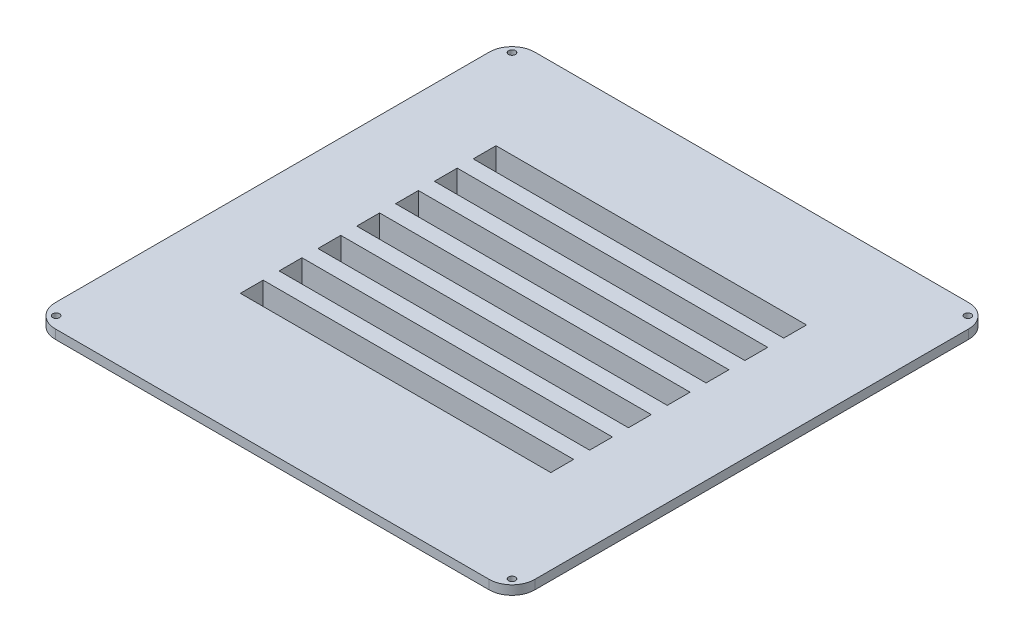
SolidWorks part; units mm, degrees
ref_plane "Front Plane" through (0, 0, 0) normal (0, 0, 1) x (1, 0, 0)
ref_plane "Top Plane" through (0, 0, 0) normal (0, 1, 0) x (1, 0, 0)
ref_plane "Right Plane" through (0, 0, 0) normal (1, 0, 0) x (0, 0, -1)
sketch "Sketch1" plane through (0, 0, 0) normal (0, 1, 0) x (1, 0, 0)
  line L0 (-101, -101) -> (-101, 101)
  line L5 (-105, -105) -> (105, -105)
  line L6 (-105, -105) -> (-105, 105)
  line L7 (-105, 105) -> (105, 105)
  line L8 (105, -105) -> (105, 105)
  line L9 (-101, 101) -> (101, 101)
  line L10 (101, -101) -> (101, 101)
  line L11 (-101, -101) -> (101, -101)
  line L12 (-101, 101) -> (-99.8333, 99.8333) construction
  line L13 (-55, 0) -> (55, 0) construction
  line L14 (-101, -101) -> (-99.8333, -99.8333) construction
  line L15 (0, -55) -> (0, 55) construction
  line L16 (101, -101) -> (99.8333, -99.8333) construction
  line L17 (101, 101) -> (99.8333, 99.8333) construction
  circle A1 centre (-99.8333, 99.8333) radius 1.5
  circle A2 centre (-99.8333, -99.8333) radius 1.5
  circle A3 centre (99.8333, -99.8333) radius 1.5
  circle A4 centre (99.8333, 99.8333) radius 1.5
  point P0 (0, 0)
  point P6 (-105, 0)
  point P7 (0, 105)
  dimension "D3" = 4
  dimension "D4" = 3
  dimension "D1" = 210
  dimension "D2" = 210
  dimension "D5" = 1.65
  dimension "D6" = 45
extrude "MainExtrude" add sketch "Sketch1" along normal blind 4 contours L6 L5 L8 L7
extrude "ScrewHoles" cut sketch "Sketch1<6>" along normal up to surface (4 mm away) contours A1 | A2 | A3 | A4 up to face at (0, 4, 0)
sketch "Sketch1<6>" plane through (0, 0, 0) normal (0, 1, 0) x (1, 0, 0) same geometry as "Sketch1"
fillet "RoundedCorners" radius 10 4 edges at (-105, 2, -105) (-105, 2, 105) (105, 2, -105) (105, 2, 105)
sketch "Sketch3" plane through (0, 0, 0) normal (0, 1, 0) x (1, 0, 0)
  line L2 (-68, 61) -> (-68, 51)
  line L4 (68, 61) -> (68, 51)
  line L17 (-68, 56) -> (68, 56) construction
  line L19 (-68, 39) -> (68, 39) construction
  line L21 (-68, 22) -> (68, 22) construction
  line L23 (-68, 5) -> (68, 5) construction
  line L24 (-68, 51) -> (68, 51)
  line L30 (-68, -12) -> (68, -12) construction
  line L32 (-68, -29) -> (68, -29) construction
  line L34 (-68, -46) -> (68, -46) construction
  line L58 (-68, 34) -> (68, 34)
  line L59 (-68, 17) -> (68, 17)
  line L60 (-68, 0) -> (68, 0)
  line L61 (-68, -17) -> (68, -17)
  line L62 (-68, -34) -> (68, -34)
  line L65 (-68, -51) -> (68, -51)
  line L66 (-68, 61) -> (68, 61)
  line L97 (-68, 44) -> (68, 44)
  line L98 (-68, 27) -> (68, 27)
  line L106 (-68, 10) -> (68, 10)
  line L107 (-68, -7) -> (68, -7)
  line L135 (-68, -24) -> (68, -24)
  line L136 (-68, -41) -> (68, -41)
  line L140 (68, 44) -> (68, 34)
  line L141 (-68, 44) -> (-68, 34)
  line L142 (-68, 27) -> (-68, 17)
  line L143 (68, 27) -> (68, 17)
  line L144 (-68, 10) -> (-68, 0)
  line L145 (68, 10) -> (68, 0)
  line L146 (-68, -7) -> (-68, -17)
  line L147 (68, -7) -> (68, -17)
  line L148 (-68, -24) -> (-68, -34)
  line L149 (68, -24) -> (68, -34)
  line L150 (-68, -41) -> (-68, -51)
  line L151 (68, -41) -> (68, -51)
  point P47 (0, 0)
  dimension "D1" = 5
  dimension "D2" = 5
  dimension "D3" = 17
  dimension "D4" = 17
  dimension "D5" = 17
  dimension "D6" = 17
  dimension "D7" = 17
  dimension "D8" = 17
  dimension "D9" = 136
sketch "Sketch4" plane through (0, 0, 0) normal (0, 1, 0) x (1, 0, 0)
  line L1 (-68, -51) -> (68, -51) construction
  line L2 (-68, -46) -> (68, -46) construction
  line L3 (-68, -41) -> (68, -41) construction
  line L4 (-68, -34) -> (68, -34) construction
  line L5 (-68, -29) -> (68, -29) construction
  line L6 (-68, -24) -> (68, -24) construction
  line L7 (-68, -17) -> (68, -17) construction
  line L8 (-68, -12) -> (68, -12) construction
  line L9 (-68, -7) -> (68, -7) construction
  line L10 (-68, 0) -> (68, 0) construction
  line L11 (-68, 5) -> (68, 5) construction
  line L12 (-68, 10) -> (68, 10) construction
  line L13 (-68, 17) -> (68, 17) construction
  line L14 (-68, 22) -> (68, 22) construction
  line L15 (-68, 27) -> (68, 27) construction
  line L16 (-68, 34) -> (68, 34) construction
  line L17 (-68, 39) -> (68, 39) construction
  line L18 (-68, 44) -> (68, 44) construction
  line L19 (68, 61) -> (68, 51) construction
  line L20 (-68, 51) -> (68, 51) construction
  line L21 (-68, 56) -> (68, 56) construction
  line L22 (-68, 61) -> (68, 61) construction
  line L23 (-68, 61) -> (-68, 51) construction
  line L26 (-68, -51) -> (68, -51)
  line L27 (-68, -46) -> (68, -46) construction
  line L28 (-68, -41) -> (68, -41)
  line L29 (-68, -34) -> (68, -34)
  line L30 (-68, -29) -> (68, -29) construction
  line L31 (-68, -24) -> (68, -24)
  line L32 (-68, -17) -> (68, -17)
  line L33 (-68, -12) -> (68, -12) construction
  line L34 (-68, -7) -> (68, -7)
  line L35 (-68, 0) -> (68, 0)
  line L36 (-68, 5) -> (68, 5) construction
  line L37 (-68, 10) -> (68, 10)
  line L38 (-68, 17) -> (68, 17)
  line L39 (-68, 22) -> (68, 22) construction
  line L40 (-68, 27) -> (68, 27)
  line L41 (-68, 34) -> (68, 34)
  line L42 (-68, 39) -> (68, 39) construction
  line L43 (-68, 44) -> (68, 44)
  line L44 (68, 61) -> (68, 51)
  line L45 (-68, 51) -> (68, 51)
  line L46 (-68, 56) -> (68, 56) construction
  line L47 (-68, 61) -> (68, 61)
  line L48 (-68, 61) -> (-68, 51)
  line L50 (68, 44) -> (68, 34)
  line L51 (-68, 44) -> (-68, 34)
  line L52 (-68, 27) -> (-68, 17)
  line L53 (68, 27) -> (68, 17)
  line L54 (-68, 10) -> (-68, 0)
  line L55 (68, 10) -> (68, 0)
  line L56 (-68, -7) -> (-68, -17)
  line L57 (68, -7) -> (68, -17)
  line L58 (-68, -24) -> (-68, -34)
  line L59 (68, -24) -> (68, -34)
  line L60 (-68, -41) -> (-68, -51)
  line L61 (68, -41) -> (68, -51)
  line L62 (-70, 63) -> (70, 63)
  line L63 (70, 63) -> (70, 49)
  line L64 (-70, 49) -> (70, 49)
  line L65 (-70, 63) -> (-70, 49)
  line L66 (-70, 46) -> (70, 46)
  line L67 (70, 46) -> (70, 32)
  line L68 (-70, 32) -> (70, 32)
  line L69 (-70, 46) -> (-70, 32)
  line L70 (-70, 29) -> (70, 29)
  line L71 (70, 29) -> (70, 15)
  line L72 (-70, 15) -> (70, 15)
  line L73 (-70, 29) -> (-70, 15)
  line L74 (-70, 12) -> (-70, -2)
  line L75 (-70, -2) -> (70, -2)
  line L76 (70, 12) -> (70, -2)
  line L77 (-70, 12) -> (70, 12)
  line L78 (-70, -5) -> (70, -5)
  line L79 (70, -5) -> (70, -19)
  line L80 (-70, -19) -> (70, -19)
  line L81 (-70, -5) -> (-70, -19)
  line L82 (-70, -22) -> (70, -22)
  line L83 (70, -22) -> (70, -36)
  line L84 (-70, -36) -> (70, -36)
  line L85 (-70, -22) -> (-70, -36)
  line L86 (-70, -39) -> (70, -39)
  line L87 (70, -39) -> (70, -53)
  line L88 (-70, -53) -> (70, -53)
  line L89 (-70, -39) -> (-70, -53)
  dimension "D1" = 2
extrude "Trench Walls" add sketch "Sketch4" against normal blind 10
extrude "Trench" cut sketch "Sketch3" along normal blind 12
sketch "Sketch6" plane through (0, -10, 0) normal (0, -1, 0) x (1, 0, 0)
  line L0 (-70, -49) -> (-70, -63) construction
  line L1 (-70, -63) -> (70, -63) construction
  line L2 (70, -63) -> (70, -49) construction
  line L3 (70, -49) -> (-70, -49) construction
  line L4 (-70, -32) -> (-70, -46) construction
  line L5 (-70, -46) -> (70, -46) construction
  line L6 (70, -46) -> (70, -32) construction
  line L7 (70, -32) -> (-70, -32) construction
  line L8 (-70, -15) -> (-70, -29) construction
  line L9 (-70, -29) -> (70, -29) construction
  line L10 (70, -29) -> (70, -15) construction
  line L11 (70, -15) -> (-70, -15) construction
  line L12 (-70, -12) -> (70, -12) construction
  line L13 (70, -12) -> (70, 2) construction
  line L14 (70, 2) -> (-70, 2) construction
  line L15 (-70, 2) -> (-70, -12) construction
  line L16 (-70, 19) -> (-70, 5) construction
  line L17 (-70, 5) -> (70, 5) construction
  line L18 (70, 5) -> (70, 19) construction
  line L19 (70, 19) -> (-70, 19) construction
  line L20 (-70, 36) -> (-70, 22) construction
  line L21 (-70, 22) -> (70, 22) construction
  line L22 (70, 22) -> (70, 36) construction
  line L23 (70, 36) -> (-70, 36) construction
  line L24 (-70, 53) -> (-70, 39) construction
  line L25 (-70, 39) -> (70, 39) construction
  line L26 (70, 39) -> (70, 53) construction
  line L27 (70, 53) -> (-70, 53) construction
  line L28 (-70, -49) -> (-70, -63)
  line L29 (-70, -63) -> (70, -63)
  line L30 (70, -63) -> (70, -49)
  line L31 (70, -49) -> (-70, -49)
  line L32 (-70, -32) -> (-70, -46)
  line L33 (-70, -46) -> (70, -46)
  line L34 (70, -46) -> (70, -32)
  line L35 (70, -32) -> (-70, -32)
  line L36 (-70, -15) -> (-70, -29)
  line L37 (-70, -29) -> (70, -29)
  line L38 (70, -29) -> (70, -15)
  line L39 (70, -15) -> (-70, -15)
  line L40 (-70, -12) -> (70, -12)
  line L41 (70, -12) -> (70, 2)
  line L42 (70, 2) -> (-70, 2)
  line L43 (-70, 2) -> (-70, -12)
  line L44 (-70, 19) -> (-70, 5)
  line L45 (-70, 5) -> (70, 5)
  line L46 (70, 5) -> (70, 19)
  line L47 (70, 19) -> (-70, 19)
  line L48 (-70, 36) -> (-70, 22)
  line L49 (-70, 22) -> (70, 22)
  line L50 (70, 22) -> (70, 36)
  line L51 (70, 36) -> (-70, 36)
  line L52 (-70, 53) -> (-70, 39)
  line L53 (-70, 39) -> (70, 39)
  line L54 (70, 39) -> (70, 53)
  line L55 (70, 53) -> (-70, 53)
extrude "Trench Bottom" add sketch "Sketch6" along normal blind 2
equation "\"1_LED\"= 17mm"
equation "\"2_LED\"= \"1_LED\" * 2"
equation "\"3_LED\"= \"1_LED\" * 3"
equation "\"4_LED\"= \"1_LED\" * 4"
equation "\"5_LED\"= \"1_LED\" * 5"
equation "\"6_LED\"= \"1_LED\" * 6"
equation "\"7_LED\"= \"1_LED\" * 7"
equation "\"8_LED\"= \"1_LED\" * 8"
equation "\"9_LED\"= \"1_LED\" * 9"
equation "\"10_LED\"= \"1_LED\" * 10"
equation "\"11_LED\"= \"1_LED\" * 11"
equation "\"12_LED\"= \"1_LED\" * 12"
